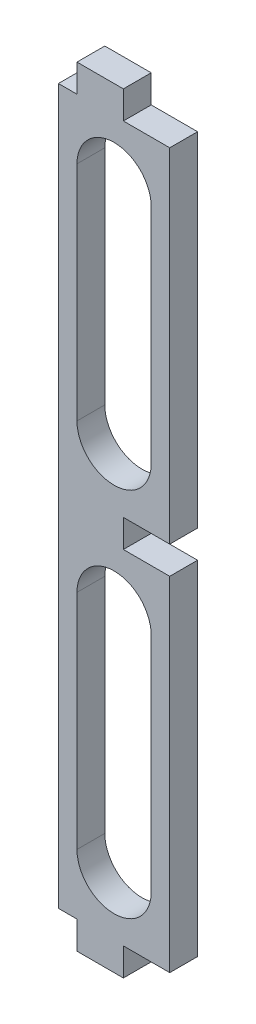
SolidWorks part; units mm, degrees
ref_plane "Plan de face" through (0, 0, 0) normal (0, 0, 1) x (1, 0, 0)
ref_plane "Plan de dessus" through (0, 0, 0) normal (0, 1, 0) x (1, 0, 0)
ref_plane "Plan de droite" through (0, 0, 0) normal (1, 0, 0) x (0, 0, -1)
sketch "Esquisse1" plane through (0, 0, 0) normal (0, 0, 1) x (1, 0, 0)
  line L0 (-6, 0) -> (6, 0)
  line L1 (6, 0) -> (6, 118) construction
  line L2 (6, 118) -> (-6, 118)
  line L3 (-6, 118) -> (-6, 0)
  line L4 (0, 118) -> (0, 0) construction
  line L10 (6, 100.5) -> (1, 100.5)
  line L11 (1, 100.5) -> (1, 97.5)
  line L12 (1, 97.5) -> (6, 97.5)
  line L13 (6, 97.5) -> (6, 60.5)
  line L14 (6, 60.5) -> (1, 60.5)
  line L15 (1, 60.5) -> (1, 57.5)
  line L16 (1, 57.5) -> (6, 57.5)
  line L17 (6, 57.5) -> (6, 20.5)
  line L18 (6, 20.5) -> (1, 20.5)
  line L19 (1, 20.5) -> (1, 17.5)
  line L20 (1, 17.5) -> (6, 17.5)
  line L25 (6, 17.5) -> (6, 0)
  line L26 (1, 99) -> (6, 99) construction
  line L27 (1, 59) -> (6, 59) construction
  line L28 (1, 19) -> (6, 19) construction
  line L29 (0, 51) -> (0, 27) construction
  line L30 (4, 51) -> (4, 27)
  line L31 (-4, 51) -> (-4, 27)
  line L32 (3.5, 298) -> (3.5, 99) construction
  line L33 (3.5, 99) -> (3.5, 59) construction
  line L34 (3.5, 59) -> (3.5, 19) construction
  line L35 (3.5, 19) -> (3.5, -180) construction
  line L36 (3.5, 298) -> (3.5, 118) construction
  line L37 (0, 67) -> (0, 91) construction
  line L38 (6, 118) -> (6, 100.5)
  line L39 (4, 67) -> (4, 91)
  line L40 (-4, 67) -> (-4, 91)
  arc A0 (4, 51) -> (-4, 51) centre (0, 51) ccw
  arc A1 (-4, 27) -> (4, 27) centre (0, 27) ccw
  arc A2 (4, 67) -> (-4, 67) centre (0, 67) cw
  arc A3 (-4, 91) -> (4, 91) centre (0, 91) cw
  point P10 (0, 39)
  point P34 (0, 79)
  point P46 (-0.4418, 19)
  circle B0 centre (0, 105) radius 1.5 construction
  circle B1 centre (0, 93) radius 1.5 construction
  line B2 (-9.0699, 99) -> (8.1862, 99) construction
  circle B3 centre (0, 65) radius 1.5 construction
  circle B4 centre (0, 53) radius 1.5 construction
  line B5 (-9.0699, 59) -> (8.1862, 59) construction
  circle B6 centre (0, 25) radius 1.5 construction
  circle B7 centre (0, 13) radius 1.5 construction
  line B8 (-9.0699, 19) -> (8.1862, 19) construction
  dimension "D7" = 24
  dimension "D6" = 2
  dimension "D1" = 40
  dimension "D2" = 17.5
  dimension "D3" = 3
  dimension "D4" = 12
  dimension "D5" = 5
  dimension "D8" = 8
sketch_block_instance "Bloc1-2"
sketch_block "Bloc1" parameters "D1"=3, "D3"=3, "D2"=12
sketch_block_instance "Bloc1-3"
sketch_block_instance "Bloc1-5"
extrude "Boss.-Extru.1" add sketch "Esquisse1" along normal blind 3
sketch "Esquisse2" plane through (0, 0, 3) normal (0, 0, 1) x (1, 0, 0)
  line L0 (-6, 118) -> (-6, 0) construction
  line L1 (-6, 118) -> (6, 118)
  line L2 (-6, 118) -> (-6, 100.5)
  line L3 (-6, 100.5) -> (6, 100.5) construction
  line L4 (6, 118) -> (6, 100.5)
  line L5 (-6, 0) -> (6, 0)
  line L6 (-6, 0) -> (-6, 17.5)
  line L7 (-6, 17.5) -> (6, 17.5) construction
  line L8 (6, 0) -> (6, 17.5)
  line L9 (-6, 20.5) -> (-4, 20.5)
  line L10 (-6, 20.5) -> (-6, 17.5)
  line L11 (-6, 17.5) -> (-4, 17.5) construction
  line L12 (-4, 20.5) -> (-4, 17.5)
  line L13 (-5, 17.5) -> (-5, 20.5) construction
  line L14 (-6, 19) -> (-4, 19) construction
  line L15 (1, 20.5) -> (6, 20.5) construction
  line L16 (1, 17.5) -> (1, 20.5) construction
  line L17 (1, 59) -> (-6, 59) construction
  line L18 (1, 57.5) -> (1, 60.5) construction
  line L19 (-6, 100.5) -> (-4, 100.5) construction
  line L20 (-4, 97.5) -> (-4, 100.5)
  line L21 (-6, 97.5) -> (-4, 97.5)
  line L22 (-6, 97.5) -> (-6, 100.5)
  line L23 (-4, 100.5) -> (6, 100.5)
  line L24 (-4, 17.5) -> (6, 17.5)
  point P111 (-5, 19)
  dimension "D1" = 5
extrude "Enlèv. mat.-Extru.1" cut sketch "Esquisse2" against normal through all
